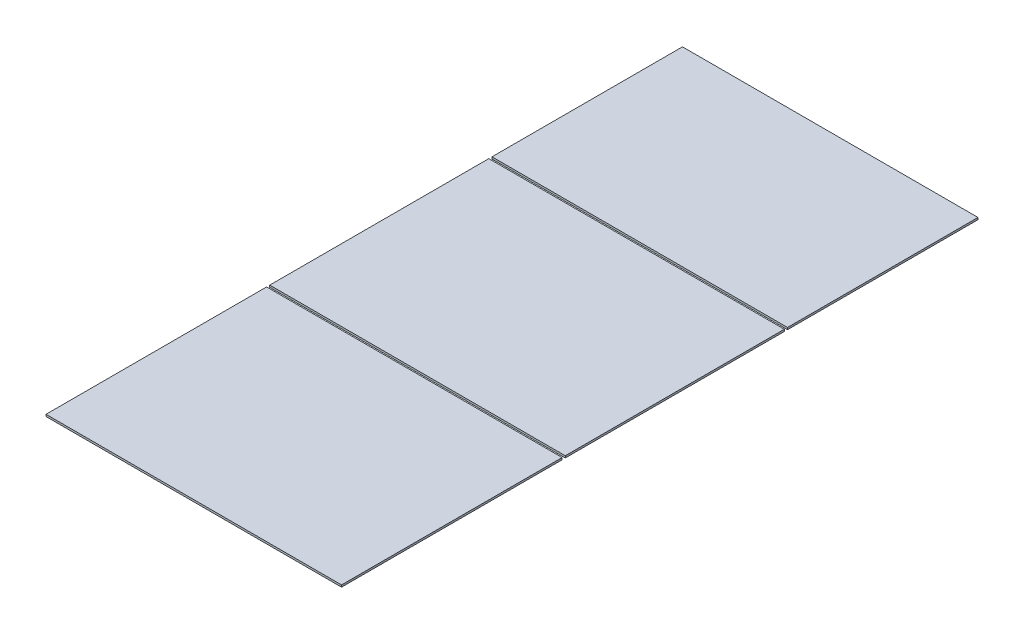
SolidWorks part; units mm, degrees
ref_plane "Front Plane" through (0, 0, 0) normal (0, 0, 1) x (1, 0, 0)
ref_plane "Top Plane" through (0, 0, 0) normal (0, 1, 0) x (1, 0, 0)
ref_plane "Right Plane" through (0, 0, 0) normal (1, 0, 0) x (0, 0, -1)
sketch "Sketch1" plane through (0, 0, 0) normal (0, 1, 0) x (1, 0, 0)
  line L0 (0, 0) -> (0, -233.332) construction
  line L1 (-368.3, 329.532) -> (368.3, 329.532)
  line L2 (-368.3, 329.532) -> (-368.3, 800.1)
  line L3 (-368.3, 800.1) -> (368.3, 800.1)
  line L4 (368.3, 329.532) -> (368.3, 800.1)
  line L5 (-368.3, 329.532) -> (368.3, 800.1) construction
  line L6 (-368.3, 800.1) -> (368.3, 329.532) construction
  line L7 (0, -233.332) -> (0, -253.332) construction
  line L8 (0, -253.332) -> (0, -800.1) construction
  line L9 (0, 0) -> (0, 309.532) construction
  line L10 (0, 309.532) -> (0, 329.532) construction
  line L11 (-368.3, -800.1) -> (368.3, -800.1)
  line L12 (-368.3, -800.1) -> (-368.3, -253.332)
  line L13 (-368.3, -253.332) -> (368.3, -253.332)
  line L14 (368.3, -800.1) -> (368.3, -253.332)
  line L15 (0, 329.532) -> (0, 800.1) construction
  line L23 (368.3, -233.332) -> (-368.3, -233.332)
  line L24 (368.3, -233.332) -> (368.3, 309.532)
  line L25 (368.3, 309.532) -> (-368.3, 309.532)
  line L26 (-368.3, -233.332) -> (-368.3, 309.532)
  point P9 (0, 0)
  point P12 (0, 0)
  point P13 (0, 0)
  point P14 (0, 0)
  point P15 (0, 0)
  point P16 (0, 0)
  point P17 (0, 0)
  dimension "D1" = 546.768
  dimension "D2" = 20
  dimension "D3" = 542.864
  dimension "D4" = 20
  dimension "D5" = 470.568
  dimension "D6" = 309.532
  dimension "D7" = 736.6
extrude "Boss-Extrude1" add sketch "Sketch1" along normal blind 2.5 and the other way blind 2.5
sketch "Sketch2" plane through (0, 0, 0) normal (0, 1, 0) x (1, 0, 0)
  line L5 (-368.3, 800.1) -> (368.3, 800.1)
  line L6 (-368.3, 800.1) -> (-368.3, 329.532)
  line L11 (-368.3, 329.532) -> (368.3, 329.532)
  line L12 (368.3, 800.1) -> (368.3, 329.532)
  line L13 (-368.3, -253.332) -> (368.3, -253.332)
  line L14 (-368.3, -253.332) -> (-368.3, -800.1)
  line L15 (-368.3, -800.1) -> (368.3, -800.1)
  line L16 (368.3, -253.332) -> (368.3, -800.1)
  line L17 (-374.3, 806.1) -> (374.3, 806.1)
  line L18 (-374.3, 806.1) -> (-374.3, 323.532)
  line L19 (-374.3, 323.532) -> (374.3, 323.532)
  line L20 (374.3, 806.1) -> (374.3, 323.532)
  line L21 (374.3, -806.1) -> (-374.3, -806.1)
  line L22 (374.3, -806.1) -> (374.3, -247.332)
  line L23 (374.3, -247.332) -> (-374.3, -247.332)
  line L24 (-374.3, -806.1) -> (-374.3, -247.332)
  line L25 (-368.3, 309.532) -> (368.3, 309.532)
  line L26 (-368.3, 309.532) -> (-368.3, -233.332)
  line L27 (-368.3, -233.332) -> (368.3, -233.332)
  line L28 (368.3, 309.532) -> (368.3, -233.332)
  line L29 (-374.3, 315.532) -> (374.3, 315.532)
  line L30 (-374.3, 315.532) -> (-374.3, -239.332)
  line L31 (-374.3, -239.332) -> (374.3, -239.332)
  line L32 (374.3, 315.532) -> (374.3, -239.332)
  dimension "D1" = 6
  dimension "D2" = 6
  dimension "D3" = 6
  dimension "D4" = 6
  dimension "D5" = 6
  dimension "D6" = 6
  dimension "D7" = 6
  dimension "D8" = 6
extrude "Boss-Extrude2" add sketch "Sketch2" along normal up to surface and the other way up to surface up to face at (0, 2.5, -564.816) other way up to face at (0, -2.5, -564.816)
